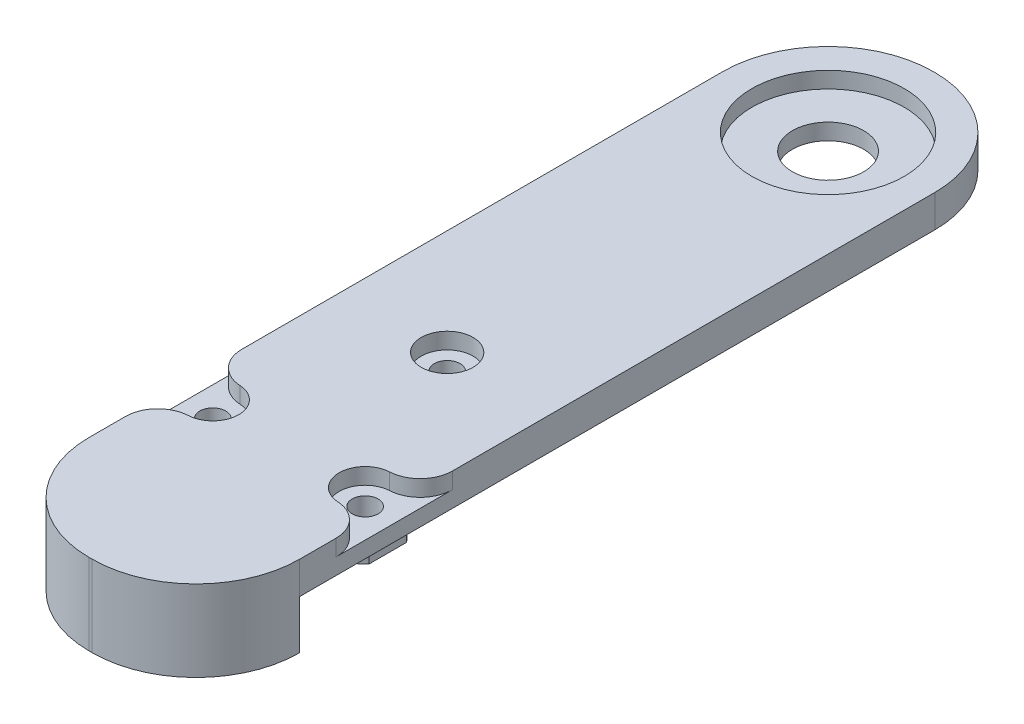
SolidWorks part; units mm, degrees
ref_plane "Front Plane" through (0, 0, 0) normal (0, 0, 1) x (1, 0, 0)
ref_plane "Top Plane" through (0, 0, 0) normal (0, 1, 0) x (1, 0, 0)
ref_plane "Right Plane" through (0, 0, 0) normal (1, 0, 0) x (0, 0, -1)
sketch "Sketch1" plane through (0, 0, 0) normal (0, 1, 0) x (1, 0, 0)
  line L1 (0, 130) -> (0.5, 130)
  line L2 (-32.5, 97.5) -> (-32.5, -98)
  line L3 (-0.5, -130) -> (0.5, -130)
  line L4 (32.5, 98) -> (32.5, -98)
  arc A0 (0, 130) -> (-32.5, 97.5) centre (0, 97.5) ccw
  arc A1 (0.5, -130) -> (32.5, -98) centre (0.5, -98) ccw
  arc A2 (-32.5, -98) -> (-0.5, -130) centre (-0.5, -98) ccw
  arc A3 (0.5, 130) -> (32.5, 98) centre (0.5, 98) cw
  point P1 (0, 0)
  dimension "D1" = 32.5
  dimension "D2" = 32
extrude "Boss-Extrude1" add sketch "Sketch1" along normal blind 10
sketch "Sketch2" plane through (0, 10, 0) normal (0, 1, 0) x (1, 0, 0)
  line L0 (0, 130) -> (0, 97.5) construction
  circle A0 centre (0, 97.5) radius 23.5
extrude "Cut-Extrude1" cut sketch "Sketch2" against normal blind 5
sketch "Sketch3" plane through (0, 5, 0) normal (0, 1, 0) x (1, 0, 0)
  circle A2 centre (0, 97.5) radius 11
  circle A3 centre (0, 97.5) radius 11
  dimension "D1" = 12.5
extrude "Cut-Extrude2" cut sketch "Sketch3" against normal through all
sketch "Sketch22" plane through (0, 0, 0) normal (0, -1, 0) x (1, 0, 0)
  circle A0 centre (0, 48.75) radius 8
extrude "Cut-Extrude15" cut sketch "Sketch22" against normal blind 4
sketch "Sketch23" plane through (0, 0, 0) normal (0, -1, 0) x (1, 0, 0)
  line L0 (-30.5, 74.6165) -> (-30.5, 62.9931)
  line L1 (-32.5, -97.5) -> (-32.5, 98) construction
  line L2 (0, -10.45) -> (0, 10.45) construction
  line L3 (30.5, 74.6165) -> (30.5, 62.9931)
  circle A1 centre (-23.5, 68.8048) radius 4
  arc A2 (-30.5, 62.9931) -> (-30.5, 74.6165) centre (-23.5, 68.8048) ccw
  circle A3 centre (23.5, 68.8048) radius 4
  arc A4 (30.5, 62.9931) -> (30.5, 74.6165) centre (23.5, 68.8048) cw
  dimension "D1" = 2
  dimension "D2" = 7
extrude "Boss-Extrude6" add sketch "Sketch23" along normal blind 4
sketch "Sketch24" plane through (0, 0, 0) normal (0, -1, 0) x (1, 0, 0)
  line L0 (-0.5, 130) -> (0.5, 130) construction
  circle A0 centre (0, 20) radius 4
  circle A2 centre (-23.5, 68.8048) radius 4
  circle A3 centre (-23.5, 68.8048) radius 4
  circle A4 centre (23.5, 68.8048) radius 4
  circle A5 centre (23.5, 68.8048) radius 4
  dimension "D1" = 0
  dimension "D3" = 110
  dimension "D2" = 0
extrude "Cut-Extrude16" cut sketch "Sketch24" against normal through all
sketch "Sketch25" plane through (0, 0, 0) normal (0, -1, 0) x (1, 0, 0)
  line L0 (-32.5, 98) -> (-30.5, 98)
  line L1 (30.5, 98) -> (32.5, 98)
  line L2 (-0.5, 128) -> (0.5, 128)
  line L3 (-0.5, 130) -> (0.5, 130)
  arc A0 (-0.5, 130) -> (-32.5, 98) centre (-0.5, 98) ccw construction
  arc A1 (-0.5, 130) -> (-32.5, 98) centre (-0.5, 98) ccw
  arc A2 (-0.5, 128) -> (-30.5, 98) centre (-0.5, 98) ccw
  arc A3 (32.5, 98) -> (0.5, 130) centre (0.5, 98) ccw construction
  arc A4 (32.5, 98) -> (0.5, 130) centre (0.5, 98) ccw
  arc A5 (30.5, 98) -> (0.5, 128) centre (0.5, 98) ccw
  dimension "D1" = 2
  dimension "D2" = 2
extrude "Boss-Extrude7" add sketch "Sketch25" along normal blind 15
sketch "Sketch26" plane through (0, 10, 0) normal (0, 1, 0) x (1, 0, 0)
  line L0 (-23.5, -60.8048) -> (-32.5, -60.8048)
  line L1 (-32.5, 97.5) -> (-32.5, -98) construction
  line L2 (-32.5, -60.8048) -> (-32.5, -76.8048)
  line L3 (-32.5, -76.8048) -> (-23.5, -76.8048)
  line L4 (0, -7.7) -> (0, 7.7) construction
  line L5 (23.5, -60.8048) -> (32.5, -60.8048)
  line L6 (32.5, -60.8048) -> (32.5, -76.8048)
  line L7 (32.5, -76.8048) -> (23.5, -76.8048)
  arc A5 (-23.5, -60.8048) -> (-23.5, -76.8048) centre (-23.5, -68.8048) cw
  arc A8 (23.5, -60.8048) -> (23.5, -76.8048) centre (23.5, -68.8048) ccw
  circle A11 centre (0, -20) radius 8
  circle A12 centre (0, -20) radius 8
  dimension "D3" = 4
extrude "Cut-Extrude17" cut sketch "Sketch26" against normal blind 5
fillet "Fillet1" radius 10 2 edges at (-32.5, 7.5, 76.8048) (-32.5, 7.5, 60.8048)
fillet "Fillet2" radius 10 2 edges at (32.5, 7.5, 76.8048) (32.5, 7.5, 60.8048)
equation "\"n\"= 60"
equation "\"p\"= 2"
equation "\"pd\"= \"n\" * \"p\" / pi"
